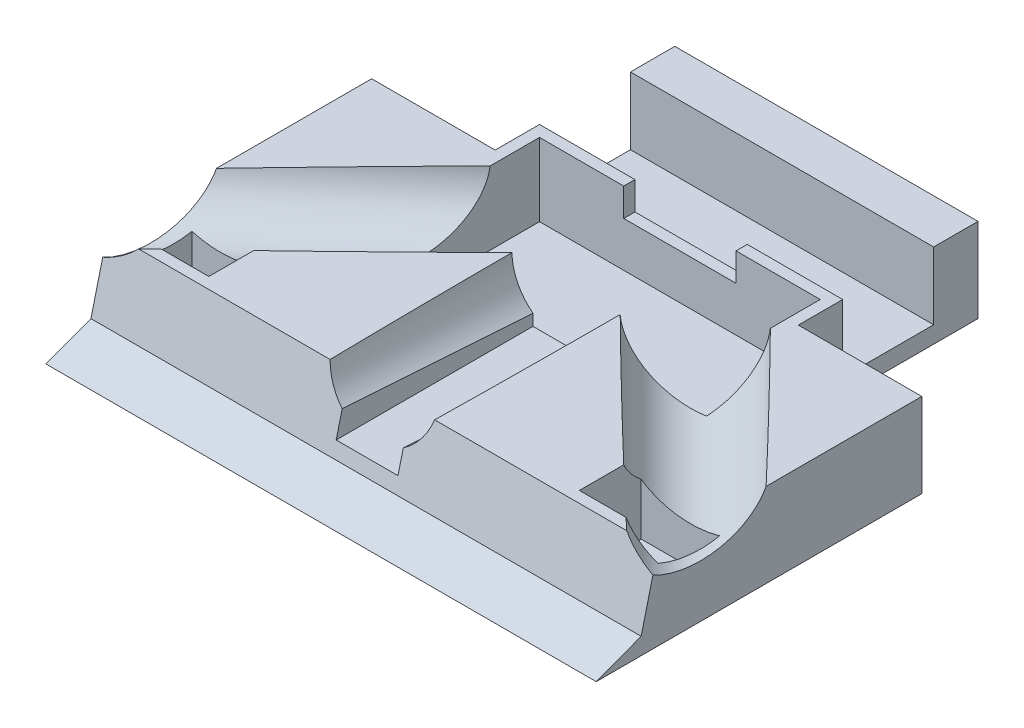
SolidWorks part; units mm, degrees
ref_plane "Front Plane" through (0, 0, 0) normal (0, 0, 1) x (1, 0, 0)
ref_plane "Top Plane" through (0, 0, 0) normal (0, 1, 0) x (1, 0, 0)
ref_plane "Right Plane" through (0, 0, 0) normal (1, 0, 0) x (0, 0, -1)
sketch "Sketch1" plane through (0, 0, 0) normal (0, 1, 0) x (1, 0, 0)
  line L1 (-41.0843, 19.8343) -> (56.9157, 19.8343)
  line L2 (-41.0843, 19.8343) -> (-41.0843, -70.1657)
  line L3 (-41.0843, -70.1657) -> (56.9157, -70.1657)
  line L4 (56.9157, 19.8343) -> (56.9157, -70.1657)
  dimension "D1" = 98
  dimension "D2" = 90
extrude "Boss-Extrude1" add sketch "Sketch1" along normal blind 15
sketch "Sketch3" plane through (0, 15, 0) normal (0, 1, 0) x (1, 0, 0)
  line L0 (-41.0843, -35.1657) -> (-6.0843, -70.1657)
  line L1 (-41.0843, 19.8343) -> (-41.0843, -70.1657) construction
  line L2 (-41.0843, -70.1657) -> (56.9157, -70.1657) construction
  line L3 (-6.0843, -70.1657) -> (-41.0843, -70.1657)
  line L4 (-41.0843, -70.1657) -> (-41.0843, -35.1657)
  line L5 (21.9157, -70.1657) -> (56.9157, -35.1657)
  line L6 (56.9157, -70.1657) -> (56.9157, 19.8343) construction
  line L7 (56.9157, -35.1657) -> (56.9157, -70.1657)
  line L8 (56.9157, -70.1657) -> (21.9157, -70.1657)
  dimension "D1" = 35
  dimension "D2" = 35
  dimension "D3" = 35
extrude "Cut-Extrude1" cut sketch "Sketch3" against normal blind 15
sketch "Sketch4" plane through (0, 15, 0) normal (0, 1, 0) x (1, 0, 0)
  line L0 (-41.0843, -35.1657) -> (-32.2419, -26.3233)
  line L1 (-32.2419, -26.3233) -> (-41.0843, -17.4808)
  line L2 (-41.0843, 19.8343) -> (-41.0843, -35.1657) construction
  line L3 (-41.0843, -17.4808) -> (-41.0843, -35.1657)
  line L4 (56.9157, -17.4808) -> (48.0733, -26.3233)
  line L5 (56.9157, -35.1657) -> (56.9157, 19.8343) construction
  line L6 (48.0733, -26.3233) -> (56.9157, -35.1657)
  line L7 (56.9157, -35.1657) -> (56.9157, -17.4808)
extrude "Cut-Extrude2" cut sketch "Sketch4" against normal blind 15
sketch "Sketch5" plane through (-2.9593, 0, -2.9593) normal (-0.7071, 0, -0.7071) x (-0.7071, 0, 0.7071)
  line L0 (53.9169, 0) -> (52.9169, 15)
  line L1 (53.9169, 15) -> (41.4118, 15) construction
  line L2 (53.9169, 15) -> (52.9169, 15)
  line L4 (53.9169, 15) -> (53.9169, 0)
  dimension "D1" = 1
extrude "Cut-Extrude5" cut sketch "Sketch5" against normal blind 100
sketch "Sketch8" plane through (10.875, 0, -10.875) normal (0.7071, 0, -0.7071) x (-0.7071, 0, -0.7071)
  line L0 (-65.1114, 0) -> (-64.1114, 15)
  line L1 (-52.6063, 15) -> (-65.1114, 15) construction
  line L2 (-64.1114, 15) -> (-65.1114, 15)
  line L3 (-65.1114, 15) -> (-65.1114, 0)
  dimension "D1" = 1
extrude "Cut-Extrude6" cut sketch "Sketch8" against normal blind 100
sketch "Sketch9" plane through (45.837, 4.3215, 45.837) normal (0.7055, 0.0665, 0.7055) x (0.7087, -0.0662, -0.7024)
  line L0 (15.6331, -3.3008) -> (-33.7552, -6.5861) construction
  circle A0 centre (-0.3647, 13.6748) radius 9.5
  dimension "D1" = 18
  dimension "D2" = 15
extrude "Cut-Extrude7" cut sketch "Sketch9" against normal blind 45
sketch "Sketch10" plane through (-37.9563, 3.5786, 37.9563) normal (-0.7055, 0.0665, 0.7055) x (0.7087, 0.0662, 0.7024)
  line L0 (44.9744, -6.5861) -> (-4.4139, -3.3008) construction
  circle A0 centre (11.452, 13.6836) radius 9.5
  dimension "D1" = 18
  dimension "D2" = 15
extrude "Cut-Extrude8" cut sketch "Sketch10" against normal blind 45
sketch "Sketch12" plane through (10.875, 0, -10.875) normal (0.7071, 0, -0.7071) x (-0.7071, 0, -0.7071)
  line L0 (-65.1114, 0) -> (-64.1114, 15)
  line L1 (-64.1114, 15) -> (-65.1114, 15)
  line L2 (-65.1114, 15) -> (-65.1114, 0)
  dimension "D1" = 1
extrude "Boss-Extrude3" add sketch "Sketch12" against normal blind 100
sketch "Sketch13" plane through (-2.9593, 0, -2.9593) normal (-0.7071, 0, -0.7071) x (-0.7071, 0, 0.7071)
  line L0 (53.9169, 0) -> (52.9169, 15)
  line L1 (52.9169, 15) -> (53.9169, 15)
  line L2 (53.9169, 15) -> (53.9169, 0)
  dimension "D1" = 1
extrude "Boss-Extrude4" add sketch "Sketch13" against normal blind 100
sketch "Sketch14" plane through (0, 15, 0) normal (0, 1, 0) x (1, 0, 0)
  line L1 (-6.0843, -70.1657) -> (48.4536, -70.1657)
  line L2 (-6.0843, -70.1657) -> (-6.0843, -107.5994)
  line L3 (-6.0843, -107.5994) -> (48.4536, -107.5994)
  line L4 (48.4536, -70.1657) -> (48.4536, -107.5994)
extrude "Cut-Extrude9" cut sketch "Sketch14" against normal blind 100
sketch "Sketch15" plane through (0, 15, 0) normal (0, 1, 0) x (1, 0, 0)
  line L2 (3.5432, -108.6479) -> (-33.6782, -108.6479)
  line L3 (3.5432, -108.6479) -> (3.5432, -76.6689)
  line L4 (3.5432, -76.6689) -> (-33.6782, -76.6689)
  line L5 (-33.6782, -108.6479) -> (-33.6782, -76.6689)
extrude "Cut-Extrude10" cut sketch "Sketch15" against normal blind 100
sketch "Sketch16" plane through (0, 15, 0) normal (0, 1, 0) x (1, 0, 0)
  line L0 (-6.0843, -70.1657) -> (-35.8986, -70.1657)
  line L1 (-41.0843, -35.1657) -> (-41.0843, -70.1657)
  line L2 (-41.0843, -70.1657) -> (-35.8986, -70.1657)
  line L3 (-41.0843, -35.1657) -> (-6.0843, -70.1657)
extrude "Boss-Extrude5" add sketch "Sketch16" against normal blind 15
sketch "Sketch17" plane through (0, 15, 0) normal (0, 1, 0) x (1, 0, 0)
  line L0 (21.9157, -70.1657) -> (49.8862, -70.1657)
  line L1 (56.9157, -35.1657) -> (56.9157, -70.1657)
  line L2 (56.9157, -70.1657) -> (49.8862, -70.1657)
  line L3 (21.9157, -70.1657) -> (56.9157, -35.1657)
extrude "Boss-Extrude6" add sketch "Sketch17" against normal blind 15
sketch "Sketch18" plane through (0, 15, 0) normal (0, 1, 0) x (1, 0, 0)
  line L0 (48.0733, -26.3233) -> (56.9157, -17.4808)
  line L1 (56.9157, -17.4808) -> (56.9157, -35.1657)
  line L2 (56.9157, -35.1657) -> (48.0733, -26.3233)
  line L3 (-41.0843, -35.1657) -> (-41.0843, -17.4808)
  line L4 (-41.0843, -17.4808) -> (-32.2419, -26.3233)
  line L5 (-32.2419, -26.3233) -> (-41.0843, -35.1657)
extrude "Boss-Extrude7" add sketch "Sketch18" against normal blind 15
sketch "Sketch19" plane through (56.9157, 0, 0) normal (1, 0, 0) x (0, 0, -1)
  line L0 (-70.1657, 0) -> (-69.1657, 15)
  line L1 (-70.1657, 15) -> (19.8343, 15) construction
  line L2 (-70.1657, 15) -> (-69.1657, 15)
  line L3 (-70.1657, 15) -> (-70.1657, 0)
  dimension "D1" = 1
extrude "Cut-Extrude11" cut sketch "Sketch19" against normal blind 100
sketch "Sketch20" plane through (0, 4.657, 69.8552) normal (0, 0.0665, 0.9978) x (1, 0, 0)
  line L0 (-41.0843, -4.6674) -> (56.9157, -4.6674) construction
  circle A0 centre (7.9157, 13.3326) radius 9.5
  point P2 (7.9157, -4.6674)
  dimension "D1" = 49
  dimension "D2" = 18
extrude "Cut-Extrude12" cut sketch "Sketch20" against normal blind 45
sketch "Sketch21" plane through (14.0876, 1.3282, 14.0876) normal (0.7055, 0.0665, 0.7055) x (0.7087, -0.0662, -0.7024)
  line L0 (-8.7092, 13.1531) -> (9.1121, 14.3386) construction
  circle A0 centre (2.2015, 13.8789) radius 9.5
  point P4 (0.2015, 13.7458)
  dimension "D1" = 2
extrude "Cut-Extrude13" cut sketch "Sketch21" along normal blind 100
sketch "Sketch22" plane through (14.0876, 1.3282, 14.0876) normal (0.7055, 0.0665, 0.7055) x (0.7087, -0.0662, -0.7024)
  circle A0 centre (-0.3647, 13.6748) radius 9.5
extrude "Boss-Extrude8" add sketch "Sketch22" along normal blind 55
sketch "Sketch23" plane through (52.8924, 4.9867, 52.8924) normal (0.7055, 0.0665, 0.7055) x (0.7024, 0.0662, -0.7087)
  circle A0 centre (4.0203, 13.465) radius 9.5
extrude "Cut-Extrude14" cut sketch "Sketch23" against normal blind 55
sketch "Sketch24" plane through (-6.207, 0.5852, 6.207) normal (-0.7055, 0.0665, 0.7055) x (0.7087, 0.0662, 0.7024)
  line L0 (1.9753, 14.3473) -> (19.9284, 13.1531) construction
  circle A0 centre (8.9518, 13.8833) radius 9.5
  point P4 (10.9518, 13.7502)
  dimension "D1" = 2
extrude "Cut-Extrude15" cut sketch "Sketch24" along normal blind 100
sketch "Sketch25" plane through (-6.207, 0.5852, 6.207) normal (-0.7055, 0.0665, 0.7055) x (0.7087, 0.0662, 0.7024)
  circle A0 centre (11.452, 13.6836) radius 9.5
extrude "Boss-Extrude10" add sketch "Sketch25" along normal blind 100
sketch "Sketch26" plane through (-6.207, 0.5852, 6.207) normal (-0.7055, 0.0665, 0.7055) x (0.7087, 0.0662, 0.7024)
  circle A0 centre (8.9518, 13.8833) radius 9.5
extrude "Cut-Extrude16" cut sketch "Sketch26" along normal blind 100
sketch "Sketch27" plane through (0, 15, 0) normal (0, 1, 0) x (1, 0, 0)
  line L1 (-41.0843, 19.8343) -> (56.9157, 19.8343)
  line L2 (-41.0843, 19.8343) -> (-41.0843, -70.1657)
  line L3 (-41.0843, -70.1657) -> (56.9157, -70.1657)
  line L4 (56.9157, 19.8343) -> (56.9157, -70.1657)
  line L5 (92.056, -99.7406) -> (-84.3219, -99.7406)
  line L6 (92.056, -99.7406) -> (92.056, 23.1019)
  line L7 (92.056, 23.1019) -> (-84.3219, 23.1019)
  line L8 (-84.3219, -99.7406) -> (-84.3219, 23.1019)
extrude "Cut-Extrude19" cut sketch "Sketch27" against normal blind 100 and the other way blind 100
sketch "Sketch28" plane through (0, 0, -19.8343) normal (0, 0, -1) x (-1, 0, 0)
  line L1 (-56.9157, 15) -> (52.5951, 15)
  line L2 (-56.9157, 15) -> (-56.9157, 39.112)
  line L3 (-56.9157, 39.112) -> (52.5951, 39.112)
  line L4 (52.5951, 15) -> (52.5951, 39.112)
extrude "Cut-Extrude20" cut sketch "Sketch28" against normal blind 100
sketch "Sketch29" plane through (0, 1.6637, 24.9549) normal (0, 0.0665, 0.9978) x (1, 0, 0)
  line L0 (4.234, 13.3659) -> (11.41, 13.3659) construction
  circle A0 centre (7.822, 13.3659) radius 9.5994
extrude "Cut-Extrude21" cut sketch "Sketch29" along normal blind 100
sketch "Sketch30" plane through (0, 15, 0) normal (0, 1, 0) x (1, 0, 0)
  line L1 (-41.0843, 19.8343) -> (-19.0843, 19.8343)
  line L2 (-41.0843, 19.8343) -> (-41.0843, -12.1657)
  line L3 (-41.0843, -12.1657) -> (-19.0843, -12.1657)
  line L4 (-19.0843, 19.8343) -> (-19.0843, -12.1657)
  line L5 (56.9157, 19.8343) -> (34.9157, 19.8343)
  line L6 (56.9157, 19.8343) -> (56.9157, -12.1657)
  line L7 (56.9157, -12.1657) -> (34.9157, -12.1657)
  line L8 (34.9157, 19.8343) -> (34.9157, -12.1657)
  dimension "D1" = 22
  dimension "D2" = 32
  dimension "D3" = 22
extrude "Cut-Extrude22" cut sketch "Sketch30" against normal blind 100
sketch "Sketch31" plane through (34.9157, 0, 0) normal (1, 0, 0) x (0, 0, -1)
  line L0 (19.8343, 15) -> (-12.1657, 15) construction
  line L1 (-4.2657, 15) -> (11.9343, 15)
  line L2 (-4.2657, 15) -> (-4.2657, 3)
  line L3 (-4.2657, 3) -> (11.9343, 3)
  line L4 (11.9343, 15) -> (11.9343, 3)
  dimension "D1" = 16.2
  dimension "D2" = 12
  dimension "D3" = 7.9
  dimension "D4" = 7.9
extrude "Cut-Extrude23" cut sketch "Sketch31" against normal blind 100
sketch "Sketch32" plane through (0, 15, 0) normal (0, 1, 0) x (1, 0, 0)
  line L0 (34.9157, -4.2657) -> (34.9157, -12.1657) construction
  line L1 (-1.776, -26.4909) -> (32.9157, -26.4909)
  line L2 (-19.0843, -4.2657) -> (34.9157, -4.2657) construction
  line L3 (-1.776, -6.2657) -> (32.9157, -6.2657)
  line L4 (32.9157, -26.4909) -> (32.9157, -6.2657)
  line L5 (-1.776, -26.4909) -> (-17.0843, -26.4909)
  line L6 (-19.0843, -12.1657) -> (-19.0843, -4.2657) construction
  line L7 (-1.776, -6.2657) -> (-17.0843, -6.2657)
  line L8 (-17.0843, -26.4909) -> (-17.0843, -6.2657)
  dimension "D1" = 2
  dimension "D2" = 2
  dimension "D3" = 2
extrude "Cut-Extrude24" cut sketch "Sketch32" against normal blind 13
sketch "Sketch33" plane through (0, 15, 0) normal (0, 1, 0) x (1, 0, 0)
  line L0 (-19.0843, -4.2657) -> (34.9157, -4.2657) construction
  line L1 (32.9157, -6.2657) -> (-17.4573, -6.2657)
  line L2 (32.9157, -6.2657) -> (32.9157, -4.2657)
  line L3 (32.9157, -4.2657) -> (-17.4573, -4.2657)
  line L4 (-17.4573, -6.2657) -> (-17.4573, -4.2657)
extrude "Boss-Extrude12" add sketch "Sketch33" against normal blind 15
sketch "Sketch34" plane through (0, 15, 0) normal (0, 1, 0) x (1, 0, 0)
  line L0 (-19.0843, -4.2657) -> (34.9157, -4.2657) construction
  line L1 (-2.0843, -4.2657) -> (17.9157, -4.2657)
  line L2 (-2.0843, -4.2657) -> (-2.0843, -6.2657)
  line L3 (-2.0843, -6.2657) -> (17.9157, -6.2657)
  line L4 (17.9157, -4.2657) -> (17.9157, -6.2657)
  line L5 (32.9157, -6.2657) -> (-17.0843, -6.2657) construction
  dimension "D1" = 20
  dimension "D2" = 17
  dimension "D3" = 17
extrude "Cut-Extrude25" cut sketch "Sketch34" against normal blind 5
sketch "Sketch35" plane through (56.9157, 0, 0) normal (1, 0, 0) x (0, 0, -1)
  line L0 (-70.1657, 0) -> (-62.1657, 3)
  line L1 (-62.1657, 3) -> (-59.1657, 15)
  line L2 (-26.4909, 15) -> (-64.3833, 15) construction
  line L3 (-59.1657, 15) -> (-69.1657, 15)
  line L4 (-69.1657, 15) -> (-70.1657, 0)
  line L5 (-70.1657, 0) -> (-12.1657, 0) construction
  dimension "D1" = 8
  dimension "D2" = 10
  dimension "D3" = 3
extrude "Cut-Extrude27" cut sketch "Sketch35" against normal blind 100
sketch "Sketch37" plane through (0, 15, 0) normal (0, 1, 0) x (1, 0, 0)
  line L0 (-41.0843, -39.8067) -> (-41.0843, -60.0609) construction
  line L1 (-25.0843, -57.1657) -> (-39.0843, -57.1657)
  line L2 (-25.0843, -57.1657) -> (-25.0843, -46.1657)
  line L3 (-25.0843, -46.1657) -> (-39.0843, -46.1657)
  line L4 (-39.0843, -57.1657) -> (-39.0843, -46.1657)
  line L5 (-35.6105, -59.1657) -> (-1.4891, -59.1657) construction
  line L6 (56.9157, -60.071) -> (56.9157, -39.9025) construction
  line L7 (40.9157, -57.1657) -> (54.9157, -57.1657)
  line L8 (40.9157, -57.1657) -> (40.9157, -46.1657)
  line L9 (40.9157, -46.1657) -> (54.9157, -46.1657)
  line L10 (54.9157, -57.1657) -> (54.9157, -46.1657)
  dimension "D1" = 11
  dimension "D2" = 14
  dimension "D3" = 2
  dimension "D4" = 2
  dimension "D5" = 14
  dimension "D6" = 2
extrude "Cut-Extrude28" cut sketch "Sketch37" against normal blind 13
sketch "Sketch38" plane through (0, 15, 0) normal (0, 1, 0) x (1, 0, 0)
  line L0 (17.4201, -26.4909) -> (-1.776, -26.4909) construction
  line L1 (1.9784, -26.4909) -> (12.9784, -26.4909)
  line L2 (1.9784, -26.4909) -> (1.9784, -60.5857)
  line L4 (12.9784, -26.4909) -> (12.9784, -60.5857)
  line L7 (1.9784, -60.5857) -> (1.9784, -67.4408)
  line L8 (1.9784, -67.4408) -> (12.9784, -67.4408)
  line L9 (12.9784, -60.5857) -> (12.9784, -67.4408)
  ellipse E0 centre (7.822, -58.5903) end of major axis (17.4214, -58.5903) minor radius 2.3657 (-1.4891, -59.1657) -> (17.1332, -59.1657) ccw construction
  dimension "D1" = 11
extrude "Cut-Extrude32" cut sketch "Sketch38" against normal blind 9.5
